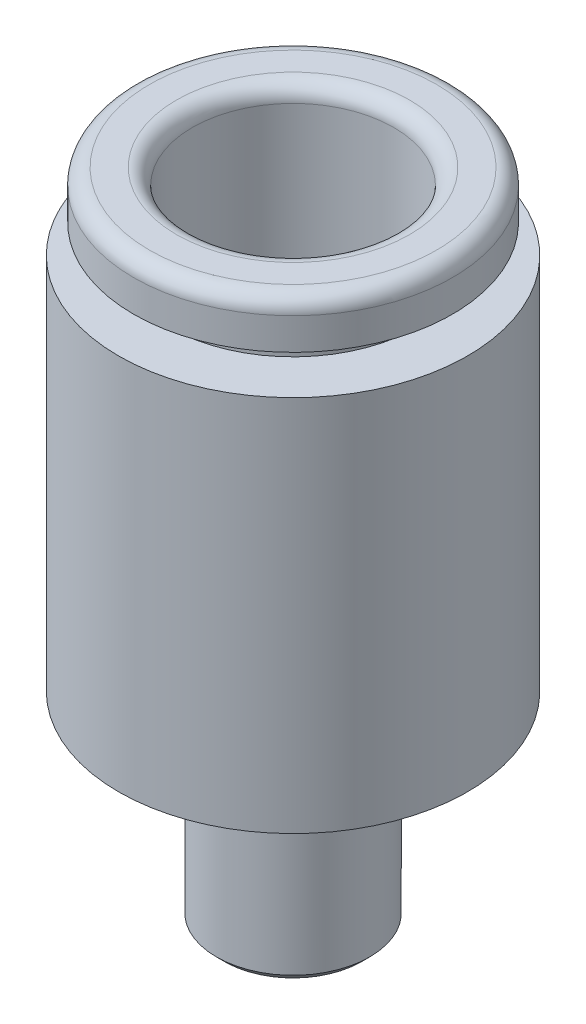
SolidWorks part; units mm, degrees
ref_plane "Front" through (0, 0, 0) normal (0, 0, 1) x (1, 0, 0)
ref_plane "Top" through (0, 0, 0) normal (0, 1, 0) x (1, 0, 0)
ref_plane "Right" through (0, 0, 0) normal (1, 0, 0) x (0, 0, -1)
ref_plane "Release_Height" through (0, -2.4, 0) normal (0, 1, 0) x (-1, 0, 0)
ref_plane "UBody_Height" through (0, -14.3, 0) normal (0, 1, 0) x (-1, 0, 0)
ref_plane "LBody_Height" through (0, -14.3, 0) normal (0, 1, 0) x (-1, 0, 0)
ref_plane "L-Total_Height" through (0, -20.6, 0) normal (0, 1, 0) x (-1, 0, 0)
ref_plane "M-Tube_Depth" through (0, -13.3, 0) normal (0, 1, 0) x (-1, 0, 0)
sketch "Release_Sketch" plane through (0, 0, 0) normal (0, 0, 1) x (1, 0, 0)
  line L0 (0, 0) -> (0, -23.4083) construction
  line L1 (0, 0) -> (-4.525, 0)
  line L2 (-5.025, -0.5) -> (-5.025, -1.5)
  line L3 (-5.025, -1.5) -> (-3.925, -1.5)
  line L4 (-3.925, -1.5) -> (-3.925, -2.4)
  line L5 (-3.925, -2.4) -> (0, -2.4)
  line L6 (14.7616, -2.4) -> (-14.7616, -2.4) construction
  line L7 (0, 0) -> (0, -2.4)
  arc A0 (-5.025, -0.5) -> (-4.525, 0) centre (-4.525, -0.5) cw
  point P12 (-5.025, 0)
  dimension "Radius" = 0.5
  dimension "Thickness" = 1.5
  dimension "Tube_Dia" = 7.85
  dimension "Outer_Dia" = 10.05
revolve "Release" add sketch "Release_Sketch" angle 360 about L0
sketch "UBody_Sketch" plane through (0, -2.4, 0) normal (0, 1, 0) x (-1, 0, 0)
  circle A0 centre (0, 0) radius 5.5
  dimension "Dia" = 11
extrude "UBody" add sketch "UBody_Sketch" against normal up to surface (11.9 mm away) up to plane "UBody_Height"
sketch "LBody_Sketch" [suppressed] plane through (0, -16, 0) normal (0, 1, 0) x (-1, 0, 0)
  circle A0 centre (0, 0) radius 3.45
  dimension "Dia" = 7
extrude "LBody" [suppressed] add sketch "LBody_Sketch" against normal up to surface (0.6 mm away)
chamfer "UBody_Chamfer" [suppressed] distance 2 angle 20
sketch "Thread_Sketch" plane through (0, 0, 0) normal (0, 0, 1) x (1, 0, 0)
  line L0 (0, 0) -> (0, -23.8143) construction
  line L1 (0, -14.3) -> (0, -2.4) construction
  line L2 (-2.415, -14.3) -> (-2.415, -20.6)
  line L3 (-2.415, -20.6) -> (0, -20.6)
  line L4 (0, -20.6) -> (0, -14.3)
  line L5 (0, -14.3) -> (-2.415, -14.3)
  line L7 (14.7616, -20.6) -> (-14.7616, -20.6) construction
  line L8 (14.7616, -14.3) -> (-14.7616, -14.3) construction
  point P13 (-2.415, -19.6)
  dimension "Taper" = 90
  dimension "a" = 1
  dimension "d" = 4.83
revolve "Thread" add sketch "Thread_Sketch" angle 360 about L0
chamfer "Thread_Chamfer" distance 0.25 angle 45 1 edges at (0, -20.6, 2.415)
chamfer "LBody_Chamfer" [suppressed] distance 2 angle 45
sketch "Tube_Sketch" plane through (0, 0, 0) normal (0, 1, 0) x (1, 0, 0)
  circle A0 centre (0, 0) radius 3.175
  dimension "Dia" = 6.35
extrude "Tube" cut sketch "Tube_Sketch" against normal up to surface (13.3 mm away) up to plane "M-Tube_Depth"
fillet "Tube_Radius" radius 0.5 1 edges at (0, 0, 3.175)
sketch "Hex_Sketch" plane through (0, -13.3, 0) normal (0, 1, 0) x (-1, 0, 0)
  line L1 (-1.1547, 0) -> (-0.5774, -1)
  line L2 (-0.5774, -1) -> (0.5774, -1)
  line L3 (0.5774, -1) -> (1.1547, 0)
  line L4 (1.1547, 0) -> (0.5774, 1)
  line L5 (0.5774, 1) -> (-0.5774, 1)
  line L6 (-0.5774, 1) -> (-1.1547, 0)
  circle A0 centre (0, 0) radius 1 construction
  dimension "Hex" = 2
extrude "Hex" cut sketch "Hex_Sketch" against normal blind 2 draft 2
sketch "Port_Sketch" plane through (0, -15.3, 0) normal (0, 1, 0) x (-1, 0, 0)
  line L0 (-1.0741, 0) -> (-0.537, -0.9302) construction
  circle A0 centre (0, 0) radius 0.9302
extrude "Port" cut sketch "Port_Sketch" against normal through all
sketch "Connecting Point" plane through (0, 0, 0) normal (0, 0, 1) x (1, 0, 0)
  line L0 (0, -14.3) -> (0, -2.4) construction
  line L1 (14.7616, 0) -> (-14.7616, 0) construction
  point P0 (0, -17.1)
  dimension "A" = 17.1
